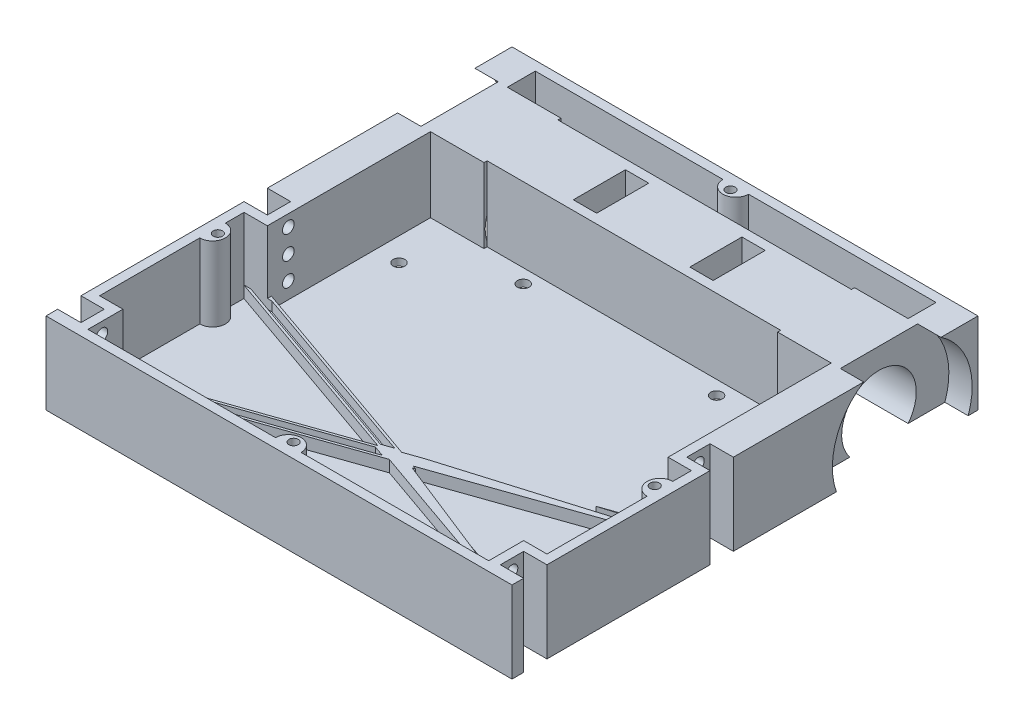
SolidWorks part; units mm, degrees
ref_plane "Plan de face" through (0, 0, 0) normal (0, 0, 1) x (1, 0, 0)
ref_plane "Plan de dessus" through (0, 0, 0) normal (0, 1, 0) x (1, 0, 0)
ref_plane "Plan de droite" through (0, 0, 0) normal (1, 0, 0) x (0, 0, -1)
sketch "Esquisse2" plane through (0, 0, 0) normal (0, 1, 0) x (1, 0, 0)
  line L1 (100, 100) -> (-100, 100)
  line L2 (100, 100) -> (100, -100)
  line L3 (100, -100) -> (-100, -100)
  line L4 (-100, 100) -> (-100, -100)
  line L5 (100, 100) -> (-100, -100) construction
  line L6 (100, -100) -> (-100, 100) construction
  point P0 (0, 0)
  dimension "D1" = 200
  dimension "D2" = 200
extrude "BASE" add sketch "Esquisse2" along normal blind 35
sketch "Esquisse3" plane through (100, 0, 0) normal (1, 0, 0) x (0, 0, -1)
  line L0 (100, 10) -> (31.0775, 10) construction
  line L1 (100, 35) -> (100, 0) construction
  line L2 (-100, 0) -> (100, 0) construction
  circle A0 centre (67.5, 10) radius 15
  point P4 (67.5, 10)
  dimension "D3" = 30
  dimension "D1" = 32.5
  dimension "D2" = 10
extrude "BLOC MOTEUR 1." cut sketch "Esquisse3" against normal blind 80
sketch "Esquisse4" plane through (0, 0, 0) normal (0, -1, 0) x (1, 0, 0)
  line L0 (20, -78.6803) -> (100, -78.6803) construction
  line L1 (20, -56.3197) -> (30, -56.3197)
  line L2 (20, -56.3197) -> (20, -78.6803)
  line L3 (20, -78.6803) -> (30, -78.6803)
  line L4 (30, -56.3197) -> (30, -78.6803)
  dimension "D1" = 10
extrude "ACCES MOTEUR" cut sketch "Esquisse4" against normal blind 37
ref_plane "PLAN SYM " through (0, 0, 0) normal (1, 0, 0) x (0, 0, -1)
sketch "Esquisse6" plane through (100, 0, 0) normal (1, 0, 0) x (0, 0, -1)
  line L0 (52.5, 10) -> (82.5, 10) construction
  arc A0 (56.3197, 20) -> (56.3197, 0) centre (67.5, 10) ccw construction
  arc A1 (78.6803, 0) -> (56.3197, 0) centre (67.5, 10) ccw construction
  circle A2 centre (67.5, 10) radius 16.01
  dimension "D1" = 32.02
extrude "BLOC MOTEUR 2" cut sketch "Esquisse6" against normal blind 37
mirror "SYM BLOC MOTEUR" about plane through (0, 0, 0) normal (1, 0, 0) of "ACCES MOTEUR", "BLOC MOTEUR 1.", "BLOC MOTEUR 2"
sketch "Esquisse7" plane through (0, 0, 0) normal (0, -1, 0) x (1, 0, 0)
  line L0 (-76, -90.0028) -> (-76, -27.4971) construction
  line L1 (-100, -54.9972) -> (-63, -54.9972) construction
  line L2 (-41.5, -56.3197) -> (-41.5, -67.469) construction
  line L3 (-63, -56.3197) -> (-20, -56.3197) construction
  line L4 (-63, -80.0028) -> (-100, -80.0028) construction
  line L5 (-20, -78.6803) -> (-63, -78.6803) construction
  line L7 (-41.5, -88.6803) -> (-41.5, -20.9291) construction
  circle A0 centre (-76, -27.4971) radius 2.5
  circle A1 centre (-41.5, -46.3197) radius 2.5
  circle A2 centre (-41.5, -88.6803) radius 2.5
  circle A3 centre (-76, -90.0028) radius 2.5
  point P8 (-64, -44.9972)
  point P9 (-76, -90.0028)
  point P10 (-41.5, -88.6803)
  point P11 (-41.5, -46.3197)
  dimension "D5" = 5
  dimension "D6" = 5
  dimension "D7" = 5
  dimension "D8" = 5
  dimension "D1" = 10
  dimension "D2" = 10
  dimension "D3" = 10
  dimension "D4" = 10
  dimension "D9" = 13
extrude "VIS MOTEUR" cut sketch "Esquisse7" against normal through all
mirror "SYM VIS" about plane through (0, 0, 0) normal (1, 0, 0) of "VIS MOTEUR"
sketch "Esquisse8" plane through (0, 0, 0) normal (0, -1, 0) x (1, 0, 0)
  line L0 (-100, 100) -> (100, 100) construction
  line L1 (-100, -54.9972) -> (-100, 100) construction
  line L2 (100, 100) -> (100, -54.9972) construction
  circle A0 centre (-55, 77.5) radius 2.5
  circle A1 centre (55, 77.5) radius 2.5
  point P0 (-55, 77.5)
  point P1 (55, 77.5)
  dimension "D5" = 5
  dimension "D6" = 5
  dimension "D1" = 22.5
  dimension "D2" = 45
  dimension "D3" = 22.5
  dimension "D4" = 45
extrude "VIS PATIN" cut sketch "Esquisse8" against normal through all
sketch "Esquisse12" plane through (-100, 0, 0) normal (-1, 0, 0) x (0, 0, 1)
  circle A0 centre (-67.5, 10) radius 30
  dimension "D1" = 60
extrude "ESPACE ROUE " cut sketch "Esquisse12" against normal blind 10
mirror "SYM ESPACE ROUE" about plane through (0, 0, 0) normal (1, 0, 0) of "ESPACE ROUE "
sketch "Esquisse23" plane through (100, 0, 0) normal (1, 0, 0) x (0, 0, -1)
  line L0 (37.5184, 11.0504) -> (37.5184, -3.5531) construction
  line L1 (-95, 35) -> (-85, 35)
  line L2 (-95, 35) -> (-95, 0)
  line L3 (-95, 0) -> (-85, 0)
  line L4 (-85, 35) -> (-85, 0)
  line L6 (-100, 0) -> (39.2157, 0) construction
  line L8 (-100, 35) -> (-100, 0) construction
  line L9 (-100, 35) -> (50.9169, 35) construction
  line L10 (-5, 0) -> (-15, 0)
  line L11 (-5, 0) -> (-5, 35)
  line L12 (-5, 35) -> (-15, 35)
  line L13 (-15, 0) -> (-15, 35)
  arc A1 (50.9169, 35) -> (39.2157, 0) centre (67.5, 10) ccw construction
  point P19 (-10, 0)
  dimension "D1" = 5
  dimension "D2" = 10
  dimension "D4" = 10
  dimension "D5" = 90
extrude "VIDE TIGE" cut sketch "Esquisse23" against normal blind 10
mirror "SYM TIGE" about plane through (0, 0, 0) normal (1, 0, 0) of "VIDE TIGE"
sketch "Esquisse25" plane through (90, 0, 0) normal (1, 0, 0) x (0, 0, -1)
  line L0 (-95, 35) -> (-85, 0) construction
  line L1 (-85, 0) -> (-90, 0) construction
  line L2 (-95, 0) -> (-85, 0) construction
  line L3 (-90, 0) -> (-90, 35) construction
  line L4 (-85, 35) -> (-95, 35) construction
  line L5 (-15, 35) -> (-85, 0) construction
  line L6 (-85, 0) -> (-85, 35) construction
  line L7 (-85, 35) -> (-50, 35) construction
  line L8 (-85, 35) -> (-15, 35) construction
  line L9 (-50, 35) -> (-50, -2.9576) construction
  circle A0 centre (-90, 30) radius 2.5
  circle A1 centre (-90, 20) radius 2.5
  circle A2 centre (-90, 10) radius 2.5
  circle A3 centre (-10, 10) radius 2.5
  circle A4 centre (-10, 30) radius 2.5
  circle A5 centre (-10, 20) radius 2.5
  dimension "D1" = 5
  dimension "D2" = 5
  dimension "D3" = 5
  dimension "D4" = 10
  dimension "D5" = 10
  dimension "D6" = 5
extrude "VIDE VIS" cut sketch "Esquisse25" against normal up to next
ref_plane "PLAN COUPE MILIEU" through (0, 4, 0) normal (0, 1, 0) x (1, 0, 0)
sketch "Esquisse27" plane through (0, 4, 0) normal (0, 1, 0) x (1, 0, 0)
  line L0 (-96, -81) -> (-96, -19)
  line L1 (-96, -19) -> (-86, -19)
  line L2 (-86, -19) -> (-86, 16.1422)
  line L3 (-86, 16.1422) -> (-86, 50.9972)
  line L4 (-86, 50.9972) -> (-63, 50.9972)
  line L5 (-63, 50.9972) -> (-63, 52.3197)
  line L6 (-63, 52.3197) -> (63, 52.3197)
  line L7 (0, -96) -> (0, 96) construction
  line L8 (86, -96) -> (-86, -96)
  line L9 (-86, -96) -> (-86, -81)
  line L10 (-86, -81) -> (-96, -81)
  line L11 (-100, -100) -> (100, -100) construction
  line L12 (-90, -85) -> (-90, -95) construction
  line L13 (-90, -85) -> (-100, -85) construction
  line L14 (-100, -15) -> (-100, -85) construction
  line L15 (-90, -15) -> (-90, -5) construction
  line L16 (-90, 54.9972) -> (-63, 54.9972) construction
  line L17 (-63, 56.3197) -> (-20, 56.3197) construction
  line L18 (-90, 80.0028) -> (-90, 95.7843) construction
  line L19 (-86, 84.0028) -> (-63, 84.0028)
  line L20 (-90, -15) -> (-100, -15) construction
  line L21 (86, 96) -> (-86, 96)
  line L22 (-86, 96) -> (-86, 84.0028)
  line L23 (100, 100) -> (-100, 100) construction
  line L24 (-63, 80.0028) -> (-90, 80.0028) construction
  line L25 (-63, 84.0028) -> (-63, 82.6803)
  line L26 (-63, 82.6803) -> (63, 82.6803)
  line L27 (63, 84.0028) -> (63, 82.6803)
  line L28 (-20, 78.6803) -> (-63, 78.6803) construction
  line L29 (86, 96) -> (86, 84.0028)
  line L30 (86, 84.0028) -> (63, 84.0028)
  line L31 (86, -81) -> (96, -81)
  line L32 (86, -96) -> (86, -81)
  line L33 (63, 50.9972) -> (63, 52.3197)
  line L34 (86, 50.9972) -> (63, 50.9972)
  line L35 (86, 16.1422) -> (86, 50.9972)
  line L36 (86, -19) -> (86, 16.1422)
  line L37 (96, -19) -> (86, -19)
  line L38 (96, -81) -> (96, -19)
  point P14 (-90, -90)
  point P48 (0, 82.6803)
  point P49 (0, 52.3197)
  dimension "D1" = 4
  dimension "D2" = 4
  dimension "D3" = 4
  dimension "D4" = 4
  dimension "D5" = 4
  dimension "D6" = 4
  dimension "D7" = 4
  dimension "D8" = 4
  dimension "D9" = 4
  dimension "D10" = 4
  dimension "D11" = 4
  dimension "D12" = 0
  dimension "D13" = 4
extrude "VIDE BASE" cut sketch "Esquisse27" along normal up to surface (31 mm away) and the other way blind 1 up to face at (-25, 35, -67.5)
sketch "Esquisse29" plane through (0, 4, 0) normal (0, 1, 0) x (1, 0, 0)
  line L0 (-100, -85) -> (100, -85) construction
  line L1 (-46.0679, -63.4751) -> (-50.724, -65.1047)
  line L2 (100, -85) -> (-100, -15) construction
  line L3 (-100, -15) -> (100, -15) construction
  line L4 (100, -15) -> (-100, -85) construction
  line L5 (-92.4323, -15) -> (0, -47.3513)
  line L6 (100, -85) -> (100, -15) construction
  line L7 (-100, -17.6487) -> (-7.5677, -50)
  line L8 (-100, -15) -> (-100, -85) construction
  line L9 (51.4875, -65.3719) -> (56.1436, -67.0016)
  line L10 (0, -50) -> (0, -85) construction
  line L11 (92.4323, -15) -> (0, -47.3513)
  line L12 (100, -17.6487) -> (7.5677, -50)
  line L13 (0, -52.6487) -> (92.4323, -85)
  line L14 (7.5677, -50) -> (51.4875, -65.3719)
  line L15 (-7.5677, -50) -> (-46.0679, -63.4751)
  line L16 (0, -52.6487) -> (-92.4323, -85)
  line L17 (-100, -82.3513) -> (-100, -85)
  line L18 (-100, -85) -> (-92.4323, -85)
  line L19 (92.4323, -85) -> (100, -85)
  line L20 (100, -85) -> (100, -82.3513)
  line L21 (92.4323, -15) -> (100, -15)
  line L22 (100, -15) -> (100, -17.6487)
  line L23 (-92.4323, -15) -> (-100, -15)
  line L24 (-100, -15) -> (-100, -17.6487)
  line L25 (-50.724, -65.1047) -> (-100, -82.3513)
  line L26 (56.1436, -67.0016) -> (100, -82.3513)
  point P4 (0, -50)
  dimension "D1" = 2.5
  dimension "D2" = 2.5
extrude "BOSS - CROIX" add sketch "Esquisse29" along normal blind 4 and the other way blind 2.5
sketch "Esquisse30" plane through (0, 35, 0) normal (0, 1, 0) x (1, 0, 0)
  line L0 (0, 0) -> (0, -96.0319) construction
  line L1 (86, -96) -> (-86, -96) construction
  line L2 (-12.2008, 96) -> (10, 96) construction
  line L3 (-5.5, -96) -> (5.5, -96) construction
  line L4 (0, 0) -> (0, 102.788) construction
  line L6 (-86, 96) -> (86, 96) construction
  line L7 (-5.5, 96) -> (5.5, 96) construction
  line L8 (-5.5, 96) -> (5.5, 96)
  line L9 (-5.5, -96) -> (5.5, -96)
  line L10 (-96, -19) -> (-96, -46) construction
  line L13 (-96, -27) -> (-96, -38)
  line L14 (96, -27) -> (96, -38)
  arc A0 (5.5, -96) -> (-5.5, -96) centre (0, -96) ccw
  circle A1 centre (0, -93.75) radius 2
  arc A2 (-5.5, 96) -> (5.5, 96) centre (0, 96) ccw
  circle A3 centre (0, 93.75) radius 2
  arc A4 (-96, -38) -> (-96, -27) centre (-96, -32.5) ccw
  circle A5 centre (-93.75, -32.5) radius 2
  circle A6 centre (93.75, -32.5) radius 2
  arc A7 (96, -38) -> (96, -27) centre (96, -32.5) cw
  point P11 (-5.5, -96)
  point P12 (10, -96)
  dimension "D1" = 11
  dimension "D3" = 4
  dimension "D4" = 11
  dimension "D5" = 4
  dimension "D7" = 11
  dimension "D8" = 4
  dimension "D2" = 2.25
  dimension "D6" = 2.25
  dimension "D9" = 2.25
extrude "BOSS VIS" add sketch "Esquisse30" against normal up to surface (35 mm away) up to face at (55, 0, 75)
sketch "Esquisse31" plane through (0, 0, 0) normal (0, -1, 0) x (1, 0, 0)
  circle A0 centre (0, 93.75) radius 2
  circle A1 centre (-93.75, 32.5) radius 2
  circle A2 centre (0, -93.75) radius 2
  circle A3 centre (93.75, 32.5) radius 2
  dimension "D1" = 4
  dimension "D2" = 4
  dimension "D3" = 4
  dimension "D4" = 4
extrude "VIDE VIS COUVERCLE" cut sketch "Esquisse31" against normal blind 5
sketch "Esquisse36" plane through (0, 4, 0) normal (0, 1, 0) x (1, 0, 0)
  line L0 (-93.1121, -81) -> (-7.5677, -51.0595)
  line L1 (-96, -81) -> (-86, -81) construction
  line L2 (-7.5677, -48.9405) -> (-93.1121, -19)
  line L3 (-10.5948, -50) -> (0, -46.2918) construction
  line L4 (-93.1121, -19) -> (-84.0308, -19)
  line L5 (-84.0308, -19) -> (-3.0271, -47.3513)
  line L6 (0, -47.3513) -> (0, -52.6487) construction
  line L7 (-93.1121, -81) -> (-84.0308, -81)
  line L8 (-84.0308, -81) -> (-3.0271, -52.6487)
  line L9 (-96, -19.0487) -> (-7.5677, -50) construction
  line L10 (-86, -17.2513) -> (0, -47.3513) construction
  line L11 (-7.5677, -50) -> (-96, -80.9513) construction
  line L12 (0, -52.6487) -> (-86, -82.7487) construction
  line L13 (-86, -19) -> (-96, -19) construction
  line L14 (-96, -80.9513) -> (-7.5677, -50) construction
  line L15 (-86, -82.7487) -> (0, -52.6487) construction
  line L16 (84.0308, -81) -> (8.0471, -50.8917)
  line L17 (84.0308, -19) -> (-2.866, -45.2887)
  line L18 (1.0636, -46.6641) -> (93.1121, -19)
  line L19 (93.1121, -81) -> (11.9767, -49.5163)
  line L20 (93.1121, -81) -> (84.0308, -81)
  line L21 (93.1121, -19) -> (84.0308, -19)
  line L22 (-7.5677, -50) -> (0, -47.3513) construction
  line L23 (0, -47.3513) -> (7.5677, -50) construction
  line L24 (7.5677, -50) -> (0, -52.6487) construction
  line L25 (0, -52.6487) -> (-7.5677, -50) construction
  line L26 (-10.5948, -50) -> (0, -53.7082) construction
  line L27 (0, -53.7082) -> (10.5948, -50) construction
  line L28 (10.5948, -50) -> (0, -46.2918) construction
  line L29 (-7.5677, -48.9405) -> (-3.0271, -47.3513)
  line L30 (-2.866, -45.2887) -> (1.0636, -46.6641)
  line L31 (11.9767, -49.5163) -> (8.0471, -50.8917)
  line L32 (-3.0271, -52.6487) -> (-7.5677, -51.0595)
  dimension "D1" = 1
  dimension "D2" = 1
  dimension "D3" = 1
  dimension "D4" = 1
  dimension "D5" = 1
  dimension "D6" = 1
  dimension "D7" = 1
  dimension "D8" = 1
extrude "VIDE CROIX" cut sketch "Esquisse36" along normal up to surface (4 mm away) up to face at (0, 8, 50)
